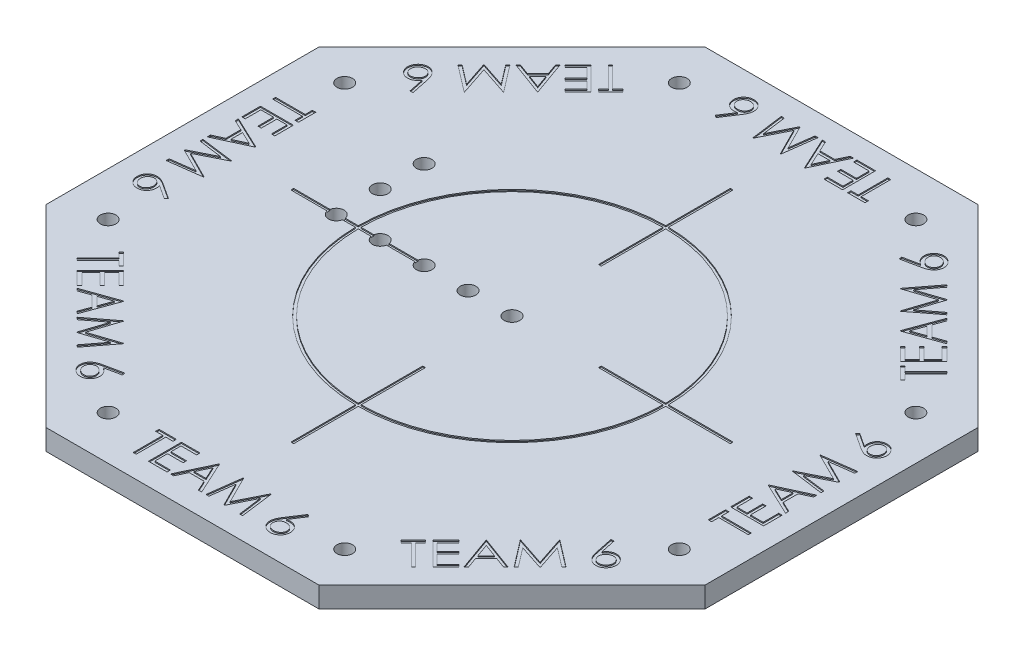
SolidWorks part; units mm, degrees
material "Custom Plastic"
ref_plane "Front Plane" through (0, 0, 0) normal (0, 0, 1) x (1, 0, 0)
ref_plane "Top Plane" through (0, 0, 0) normal (0, 1, 0) x (1, 0, 0)
ref_plane "Right Plane" through (0, 0, 0) normal (1, 0, 0) x (0, 0, -1)
ref_axis "Axis1" through (0, 6.2941, 0) along (0, -1, 0)
sketch "Sketch1" plane through (0, 0, 0) normal (0, 1, 0) x (1, 0, 0)
  line L1 (-39.4538, 95.25) -> (-95.25, 39.4538)
  line L2 (-95.25, 39.4538) -> (-95.25, -39.4538)
  line L3 (-95.25, -39.4538) -> (-39.4538, -95.25)
  line L4 (-39.4538, -95.25) -> (39.4538, -95.25)
  line L5 (39.4538, -95.25) -> (95.25, -39.4538)
  line L6 (95.25, -39.4538) -> (95.25, 39.4538)
  line L7 (95.25, 39.4538) -> (39.4538, 95.25)
  line L8 (39.4538, 95.25) -> (-39.4538, 95.25)
  circle A0 centre (0, 0) radius 95.25 construction
  dimension "D1" = 190.5
extrude "Base" add sketch "Sketch1" along normal blind 5.9944
sketch "Sketch2" plane through (0, 5.9944, 0) normal (0, 1, 0) x (1, 0, 0)
  line L0 (39.4538, 95.25) -> (-39.4538, 95.25) construction
  line L1 (34.1933, 82.55) -> (-34.1933, 82.55)
  line L2 (-34.1933, 82.55) -> (-82.55, 34.1933)
  line L3 (-82.55, 34.1933) -> (-82.55, -34.1933)
  line L4 (-82.55, -34.1933) -> (-34.1933, -82.55)
  line L5 (-34.1933, -82.55) -> (34.1933, -82.55)
  line L6 (34.1933, -82.55) -> (82.55, -34.1933)
  line L7 (82.55, -34.1933) -> (82.55, 34.1933)
  line L8 (82.55, 34.1933) -> (34.1933, 82.55)
  circle A0 centre (0, 0) radius 82.55 construction
  dimension "D1" = 12.7
hole_wizard "Mounting holes" positions "Sketch4" profile "Sketch3" hole size "#8" standard "ANSI Inch"
sketch "Sketch4" plane through (0, 5.9944, 0) normal (0, 1, 0) x (1, 0, 0)
  point P0 (-34.1933, 82.55)
  point P8 (34.1933, 82.55)
  point P11 (82.55, 34.1933)
  point P14 (82.55, -34.1933)
  point P17 (34.1933, -82.55)
  point P20 (-34.1933, -82.55)
  point P23 (-82.55, -34.1933)
  point P26 (-82.55, 34.1933)
sketch "Sketch3" plane through (-34.1933, 5.9944, -82.55) normal (1, 0, 0) x (0, 0, 1)
  line L0 (0, 0) -> (0, 5.9944)
  line L1 (0, 5.9944) -> (2.2479, 5.9944)
  line L2 (2.2479, 5.9944) -> (2.2479, 0)
  line L5 (2.2479, 0) -> (0, 0)
  line L10 (0, 5.9944) -> (-2.2479, 5.9944) construction
  line L11 (0, -6.35) -> (0, 107.95) construction
  dimension "Hole Dia." = 4.4958
  dimension "Hole Depth" = 5.9944
  dimension "Drill Angle" = 180
sketch "Sketch5" plane through (0, 5.9944, 0) normal (0, 1, 0) x (1, 0, 0)
  line L0 (0, 0) -> (-95.25, 0) construction
  line L1 (-95.25, 39.4538) -> (-95.25, -39.4538) construction
  line L2 (-50.8, 0) -> (-50.8, 25.4) construction
  point P4 (-12.7, 0)
  point P5 (-25.4, 0)
  point P7 (-38.1, 0)
  point P8 (-50.8, 0)
  point P11 (-50.8, 12.7)
  dimension "D1" = 12.7
  dimension "D2" = 12.7
  dimension "D3" = 12.7
  dimension "D4" = 12.7
  dimension "D5" = 25.4
hole_wizard "#8 Clearance Hole1" positions "Sketch7" profile "Sketch6" hole size "#8" standard "ANSI Inch" end condition through all
sketch "Sketch7" plane through (0, 5.9944, 0) normal (0, 1, 0) x (1, 0, 0)
  point P0 (0, 0)
  point P3 (-12.7, 0)
  point P6 (-25.4, 0)
  point P9 (-38.1, 0)
  point P12 (-50.8, 0)
  point P15 (-50.8, 12.7)
  point P18 (-50.8, 25.4)
sketch "Sketch6" plane through (0, 5.9944, 0) normal (1, 0, 0) x (0, 0, 1)
  line L0 (0, 0) -> (0, 5.9944)
  line L1 (0, 5.9944) -> (2.2479, 5.9944)
  line L2 (2.2479, 5.9944) -> (2.2479, 0)
  line L5 (2.2479, 0) -> (0, 0)
  line L11 (0, -6.35) -> (0, 107.95) construction
  dimension "Thru Hole Dia." = 4.4958
  dimension "Thru Hole Depth" = 5.9944
sketch "Sketch8" plane through (0, 5.9944, 0) normal (0, 1, 0) x (1, 0, 0)
  line L0 (-39.4538, -95.25) -> (39.4538, -95.25) construction
  line L2 (-45.8038, -88.9) -> (45.8038, -88.9) construction
  line L3 (-95.25, -39.4538) -> (-39.4538, -95.25) construction
  line L4 (39.4538, -95.25) -> (95.25, -39.4538) construction
  text T0 "TEAM 6" font "Century Gothic" height 9.525
  dimension "D1" = 6.35
extrude "Cut-Extrude1" cut sketch "Sketch8" against normal blind 0.3175
pattern_circular "CirPattern1" count 8 over 360 about axis through (0, 6.2941, 0) along (0, -1, 0) of "Cut-Extrude1"
sketch "Sketch9" plane through (0, 5.9944, 0) normal (0, 1, 0) x (1, 0, 0)
  line L0 (0, 63.5) -> (0, 25.4)
  line L1 (63.5, 0) -> (25.4, 0)
  line L2 (0, -63.5) -> (0, -25.4)
  line L3 (-63.5, 0) -> (-25.4, 0)
  circle A0 centre (0, 0) radius 44.45
  point P5 (0, 44.45)
  point P6 (44.45, 0)
  point P7 (0, -44.45)
  point P8 (-44.45, 0)
  point P15 (-5.4202, -4.3363)
  dimension "D1" = 88.9
  dimension "D2" = 38.1
extrude "Cut-Extrude-Thin2" cut sketch "Sketch9" against normal blind 0.3175 thin thin type mid plane wall 0.7937
equation "\"MAT_THICKNESS\"=0.236"
equation "\"D1@Base\"=\"MAT_THICKNESS\""
